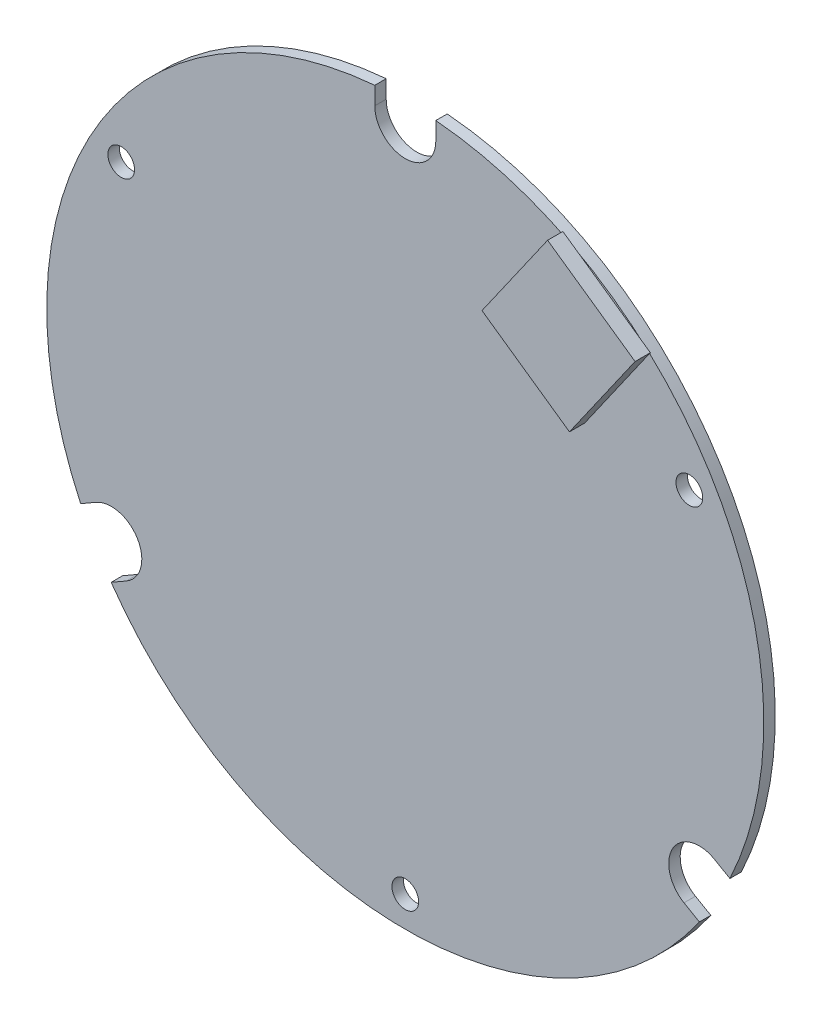
SolidWorks part; units mm, degrees
ref_plane "Alzado" through (0, 0, 0) normal (0, 0, 1) x (1, 0, 0)
ref_plane "Planta" through (0, 0, 0) normal (0, 1, 0) x (1, 0, 0)
ref_plane "Vista lateral" through (0, 0, 0) normal (1, 0, 0) x (0, 0, -1)
sketch "Croquis1" plane through (0, 0, 0) normal (0, 0, 1) x (1, 0, 0)
  line L0 (-3, 44.5) -> (-3, 47.9062) construction
  line L1 (3, 44.5) -> (3, 47.9062) construction
  line L2 (0, 44.5) -> (0, 0) construction
  line L3 (37.0381, -24.8481) -> (39.988, -26.5512) construction
  line L4 (40.0381, -19.6519) -> (42.988, -21.355) construction
  line L5 (-40.0381, -19.6519) -> (-42.988, -21.355) construction
  line L6 (-37.0381, -24.8481) -> (-39.988, -26.5512) construction
  line L7 (0, 0) -> (0, 44.5) construction
  line L8 (0, 0) -> (38.5381, -22.25) construction
  line L9 (-4, 44.5) -> (-4, 46.8295)
  line L10 (-40.5381, -18.7859) -> (-42.5555, -19.9506)
  line L11 (-36.5381, -25.7141) -> (-38.5555, -26.8788)
  line L12 (36.5381, -25.7141) -> (38.5555, -26.8788)
  line L13 (40.5381, -18.7859) -> (42.5555, -19.9506)
  line L14 (4, 44.5) -> (4, 46.8295)
  line L15 (1, 44.5) -> (1, 0)
  arc A0 (-39.988, -26.5512) -> (39.988, -26.5512) centre (0, 0) ccw construction
  arc A1 (-3, 44.5) -> (3, 44.5) centre (0, 44.5) ccw construction
  arc A2 (40.0381, -19.6519) -> (37.0381, -24.8481) centre (38.5381, -22.25) ccw construction
  arc A3 (-37.0381, -24.8481) -> (-40.0381, -19.6519) centre (-38.5381, -22.25) ccw construction
  arc A4 (42.988, -21.355) -> (3, 47.9062) centre (0, 0) ccw construction
  arc A5 (-3, 47.9062) -> (-42.988, -21.355) centre (0, 0) ccw construction
  arc A6 (-4, 46.8295) -> (-42.5555, -19.9506) centre (0, 0) ccw
  arc A7 (-36.5381, -25.7141) -> (-40.5381, -18.7859) centre (-38.5381, -22.25) ccw
  arc A8 (-38.5555, -26.8788) -> (38.5555, -26.8788) centre (0, 0) ccw
  arc A9 (40.5381, -18.7859) -> (36.5381, -25.7141) centre (38.5381, -22.25) ccw
  arc A10 (42.5555, -19.9506) -> (4, 46.8295) centre (0, 0) ccw
  arc A11 (-4, 44.5) -> (4, 44.5) centre (0, 44.5) ccw
  dimension "D1" = 96
  dimension "D2" = 44.5
  dimension "D3" = 6
  dimension "D4" = 3
  dimension "D5" = 120
  dimension "D6" = 1
extrude "Saliente-Extruir1" add sketch "Croquis1" along normal blind 1.5 contours A11 L9 A6 L10 A7 L11 A8 L12 A9 L13 A10 L14 region at (0, 0, 0)
sketch "Croquis2" plane through (0, 0, 1.5) normal (0, 0, 1) x (1, 0, 0)
  line L0 (0, 0) -> (-37.2391, 21.5) construction
  line L1 (0, 0) -> (0, 40.5) construction
  line L2 (0, 0) -> (-37.2391, 21.5) construction
  line L3 (0, 0) -> (37.2391, 21.5) construction
  circle A0 centre (-37.2391, 21.5) radius 1.75
  arc A1 (-4, 44.5) -> (4, 44.5) centre (0, 44.5) ccw construction
  circle A2 centre (37.2391, 21.5) radius 1.75
  circle A3 centre (0, -43) radius 1.75
  dimension "D1" = 3.5
  dimension "D2" = 60
  dimension "D3" = 43
  dimension "D5" = 120
  dimension "D4" = 3
extrude "Cortar-Extruir1" cut sketch "Croquis2" against normal blind 1.5
sketch "Croquis3" plane through (0, 0, 1.5) normal (0, 0, 1) x (1, 0, 0)
  line L0 (0, 0) -> (26.9581, 38.5001) construction
  line L1 (0, 0) -> (0, 40.5) construction
  line L3 (22.658, 44.5631) -> (34.1261, 36.533)
  line L4 (22.658, 44.5631) -> (14.0543, 32.2758)
  line L5 (34.1261, 36.533) -> (25.5225, 24.2457)
  line L6 (14.0543, 32.2758) -> (25.5225, 24.2457)
  line L12 (-4, 44.5) -> (-4, 46.8295)
  line L13 (-42.5555, -19.9506) -> (-40.5381, -18.7859)
  line L14 (-36.5381, -25.7141) -> (-38.5555, -26.8788)
  line L15 (38.5555, -26.8788) -> (36.5381, -25.7141)
  line L16 (40.5381, -18.7859) -> (42.5555, -19.9506)
  line L17 (4, 46.8295) -> (4, 44.5)
  line L18 (-4, 44.5) -> (-4, 46.8295) construction
  line L19 (-42.5555, -19.9506) -> (-40.5381, -18.7859) construction
  line L20 (-36.5381, -25.7141) -> (-38.5555, -26.8788) construction
  line L21 (38.5555, -26.8788) -> (36.5381, -25.7141) construction
  line L22 (40.5381, -18.7859) -> (42.5555, -19.9506) construction
  line L23 (4, 46.8295) -> (4, 44.5) construction
  arc A0 (42.5555, -19.9506) -> (4, 46.8295) centre (0, 0) ccw construction
  arc A1 (-4, 44.5) -> (4, 44.5) centre (0, 44.5) ccw construction
  arc A8 (-4, 44.5) -> (4, 44.5) centre (0, 44.5) ccw
  arc A9 (-4, 46.8295) -> (-42.5555, -19.9506) centre (0, 0) ccw
  arc A10 (-36.5381, -25.7141) -> (-40.5381, -18.7859) centre (-38.5381, -22.25) ccw
  arc A11 (-38.5555, -26.8788) -> (38.5555, -26.8788) centre (0, 0) ccw
  arc A12 (40.5381, -18.7859) -> (36.5381, -25.7141) centre (38.5381, -22.25) ccw
  arc A13 (42.5555, -19.9506) -> (4, 46.8295) centre (0, 0) ccw
  arc A14 (-4, 44.5) -> (4, 44.5) centre (0, 44.5) ccw construction
  arc A15 (-4, 46.8295) -> (-42.5555, -19.9506) centre (0, 0) ccw construction
  arc A16 (-36.5381, -25.7141) -> (-40.5381, -18.7859) centre (-38.5381, -22.25) ccw construction
  arc A17 (-38.5555, -26.8788) -> (38.5555, -26.8788) centre (0, 0) ccw construction
  arc A18 (40.5381, -18.7859) -> (36.5381, -25.7141) centre (38.5381, -22.25) ccw construction
  arc A19 (42.5555, -19.9506) -> (4, 46.8295) centre (0, 0) ccw construction
  point P12 (19.7884, 28.2607)
  dimension "D1" = 35
  dimension "D2" = 2.5
  dimension "D3" = 15
  dimension "D4" = 14
  dimension "D5" = 0
extrude "Saliente-Extruir2" add sketch "Croquis3" along normal blind 2 from offset 2 separate body
sketch "Croquis4" plane through (29.5392, 42.1863, 0) normal (0.5736, 0.8192, 0) x (0.8192, -0.5736, 0)
  line L2 (9.178, -16.3996) -> (-9.1403, -16.3996)
  line L3 (9.178, -16.3996) -> (9.178, -10.1377)
  line L4 (9.178, -10.1377) -> (-9.1403, -10.1377)
  line L5 (-9.1403, -16.3996) -> (-9.1403, -10.1377)
